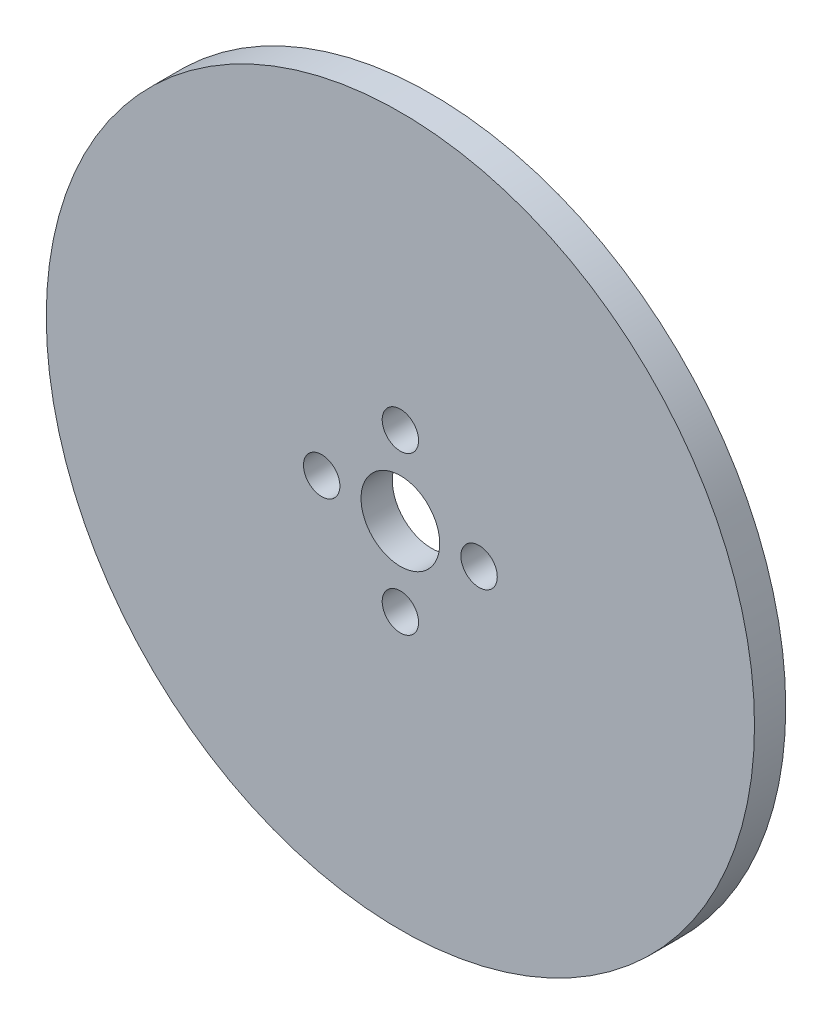
SolidWorks part; units mm, degrees
material "6061-T6 (SS)"
ref_plane "Front" through (0, 0, 0) normal (0, 0, 1) x (1, 0, 0)
ref_plane "Top" through (0, 0, 0) normal (0, 1, 0) x (1, 0, 0)
ref_plane "Right" through (0, 0, 0) normal (1, 0, 0) x (0, 0, -1)
ref_axis "side-side" through (80.9, 0, 0) along (-1, 0, 0)
ref_axis "up-down" through (0, 50, 0) along (0, -1, 0)
ref_axis "front-back" through (0, 0, -80.9) along (0, 0, 1)
sketch "Sketch1" plane through (0, 0, 0) normal (0, 0, 1) x (1, 0, 0)
  line L1 (-36, 100) -> (36, 100) construction
  line L2 (-36, 100) -> (-36, 0) construction
  line L3 (-36, 0) -> (36, 0) construction
  line L4 (36, 100) -> (36, 0) construction
  arc A0 (-36, 0) -> (36, 0) centre (0, 0) ccw
  circle A1 centre (0, 0) radius 4
  circle A2 centre (-8, 0) radius 1.85
  circle A3 centre (0, -8) radius 1.85
  circle A4 centre (0, 0) radius 8 construction
  circle A5 centre (0, 8) radius 1.85
  circle A6 centre (8, 0) radius 1.85
  arc A7 (-36, 0) -> (36, 0) centre (0, 0) cw
  dimension "D1" = 8
  dimension "D4" = 16
  dimension "D5" = 3.7
  dimension "D2" = 72
  dimension "D3" = 100
extrude "Boss-Extrude1" add sketch "Sketch1" along normal blind 3.175
